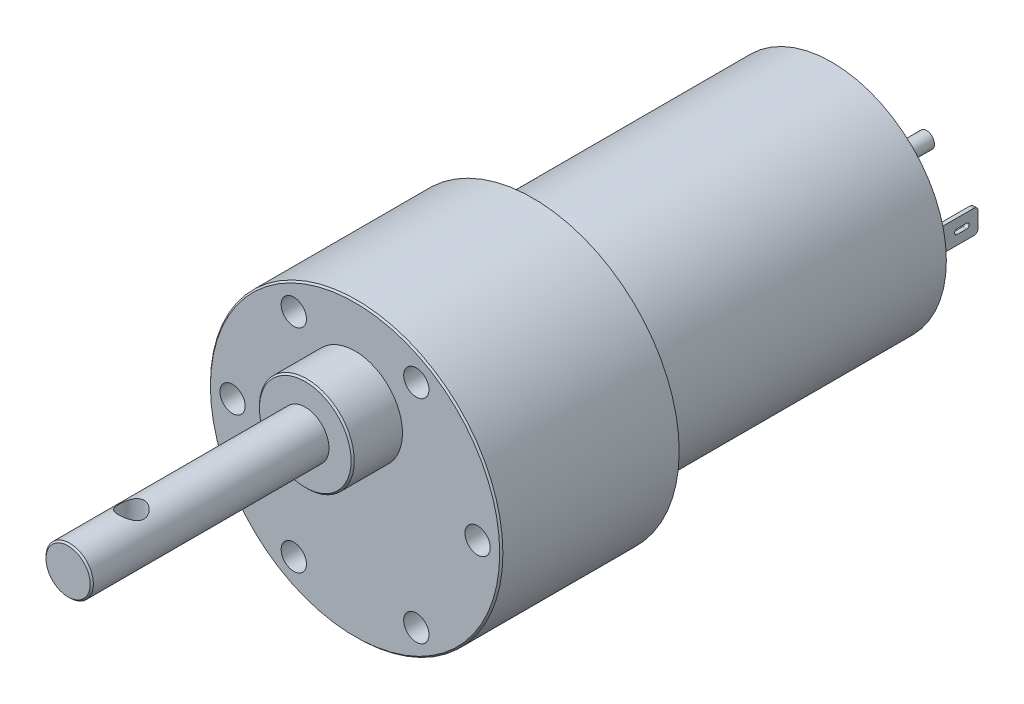
SolidWorks part; units mm, degrees
ref_plane "Front Plane" through (0, 0, 0) normal (0, 0, 1) x (1, 0, 0)
ref_plane "Top Plane" through (0, 0, 0) normal (0, 1, 0) x (1, 0, 0)
ref_plane "Right Plane" through (0, 0, 0) normal (1, 0, 0) x (0, 0, -1)
sketch "Sketch1" plane through (0, 0, 0) normal (0, 0, 1) x (1, 0, 0)
  circle A0 centre (0, 0) radius 18.5
  dimension "D1" = 37
extrude "Boss-Extrude1" add sketch "Sketch1" along normal blind 22.5
sketch "Sketch2" plane through (0, 0, 22.5) normal (0, 0, 1) x (1, 0, 0)
  line L0 (-18.5, 0) -> (18.5, 0) construction
  line L1 (0, 18.5) -> (0, -18.5) construction
  line L2 (11.1332, 19.2832) -> (-10.7359, -18.5952) construction
  line L3 (-11.3747, 19.7016) -> (11.6905, -20.2486) construction
  circle A0 centre (0, 0) radius 18.5 construction
  circle A1 centre (0, 0) radius 15.5 construction
  circle A2 centre (-7.75, 13.4234) radius 1.6
  circle A3 centre (7.75, 13.4234) radius 1.6
  circle A4 centre (-15.5, 0) radius 1.6
  circle A5 centre (-7.75, -13.4234) radius 1.6
  circle A6 centre (7.75, -13.4234) radius 1.6
  circle A7 centre (15.5, 0) radius 1.6
  dimension "D3" = 31
  dimension "D4" = 3.2
  dimension "D1" = 120
  dimension "D2" = 120
extrude "Cut-Extrude1" cut sketch "Sketch2" against normal blind 3.5
sketch "Sketch3" plane through (0, 0, 22.5) normal (0, 0, 1) x (1, 0, 0)
  line L0 (0, 0) -> (0, 18.5) construction
  circle A0 centre (0, 0) radius 18.5 construction
  circle A1 centre (0, 7) radius 6
  circle A2 centre (0, 7) radius 3
  dimension "D1" = 12
  dimension "D3" = 6
  dimension "D2" = 7
extrude "Boss-Extrude2" add sketch "Sketch3" along normal blind 36.3 contours A2 L0 | L0 A2 region at (-1.2732, 7, 22.5) region at (1.2732, 7, 22.5)
extrude "Boss-Extrude3" add sketch "Sketch3<3>" along normal blind 6.3 contours A1 L0 A2 | L0 A1 A2 region at (-5.8658, 7, 22.5) region at (0.1342, 2.5, 22.5)
sketch "Sketch3<3>" plane through (0, 0, 22.5) normal (0, 0, 1) x (1, 0, 0) same geometry as "Sketch3"
sketch "Sketch4" plane through (0, 0, 0) normal (0, 0, -1) x (-1, 0, 0)
  circle A0 centre (0, 0) radius 14.5
  dimension "D1" = 29
extrude "Boss-Extrude4" add sketch "Sketch4" along normal blind 37.8
sketch "Sketch5" plane through (0, 0, -37.8) normal (0, 0, -1) x (-1, 0, 0)
  line L0 (-14.5, 0) -> (14.5, 0) construction
  circle A0 centre (0, 0) radius 5
  circle A1 centre (0, 0) radius 14.5 construction
  dimension "D1" = 10
extrude "Boss-Extrude5" add sketch "Sketch5" along normal blind 3
sketch "Sketch6" plane through (0, 0, -40.8) normal (0, 0, -1) x (-1, 0, 0)
  circle A0 centre (0, 0) radius 1
  dimension "D1" = 2
extrude "Boss-Extrude6" add sketch "Sketch6" along normal blind 9
sketch "Sketch7" plane through (0, 0, -37.8) normal (0, 0, -1) x (-1, 0, 0)
  line L0 (-14.5, 0) -> (14.5, 0) construction
  line L1 (0, 0) -> (0, -10.7163) construction
  line L2 (-12, 1.5) -> (-11.5, 1.5)
  line L3 (-12, 1.5) -> (-12, -1.5)
  line L4 (-12, -1.5) -> (-11.5, -1.5)
  line L5 (-11.5, 1.5) -> (-11.5, -1.5)
  line L6 (12, 1.5) -> (11.5, 1.5)
  line L7 (12, -1.5) -> (11.5, -1.5)
  line L8 (12, 1.5) -> (12, -1.5)
  line L9 (11.5, 1.5) -> (11.5, -1.5)
  circle A0 centre (0, 0) radius 14.5 construction
  circle A1 centre (0, 0) radius 14.5 construction
  dimension "D1" = 3
  dimension "D2" = 1.5
  dimension "D3" = 0.5
  dimension "D4" = 11.5
extrude "Boss-Extrude7" add sketch "Sketch7" along normal blind 6.5
sketch "Sketch8" plane through (12, 0, 0) normal (1, 0, 0) x (0, 0, -1)
  line L0 (42.8651, 0) -> (41.6651, 0) construction
  line L1 (42.8651, -0.3201) -> (41.6651, -0.3201)
  line L2 (42.8651, 0.3201) -> (41.6651, 0.3201)
  line L3 (42.8651, 0) -> (44.3, 0) construction
  line L4 (44.3, 1.5) -> (44.3, -1.5) construction
  arc A0 (42.8651, -0.3201) -> (42.8651, 0.3201) centre (42.8651, 0) ccw
  arc A1 (41.6651, 0.3201) -> (41.6651, -0.3201) centre (41.6651, 0) ccw
  point P2 (42.2651, 0)
  dimension "D1" = 1.2
extrude "Cut-Extrude2" cut sketch "Sketch8" against normal blind 0.5
mirror "Mirror2" about plane through (0, 0, 0) normal (1, 0, 0) of "Cut-Extrude2"
fillet "Fillet1" radius 0.5 4 edges at (-11.75, 1.5, -44.3) (-11.75, -1.5, -44.3) (11.75, 1.5, -44.3) (11.75, -1.5, -44.3)
chamfer "Chamfer1" distance 0.2 angle 45 3 edges at (18.5, 0, 22.5) (6, 7, 28.8) (3, 7, 58.8)
ref_plane "Plane1" through (0, 7, 0) normal (0, 1, 0) x (1, 0, 0)
sketch "Sketch9" plane through (0, 7, 0) normal (0, 1, 0) x (1, 0, 0)
  line L0 (0, -58.6) -> (0, -28.8) construction
  line L1 (3, -58.6) -> (-3, -58.6) construction
  line L2 (-2.8, -58.8) -> (2.8, -58.8) construction
  line L3 (-3, -28.8) -> (3, -28.8) construction
  circle A0 centre (0, -50.8) radius 1.6
  dimension "D1" = 3.2
  dimension "D2" = 8
extrude "Cut-Extrude3" cut sketch "Sketch9" against normal through all and the other way through all
